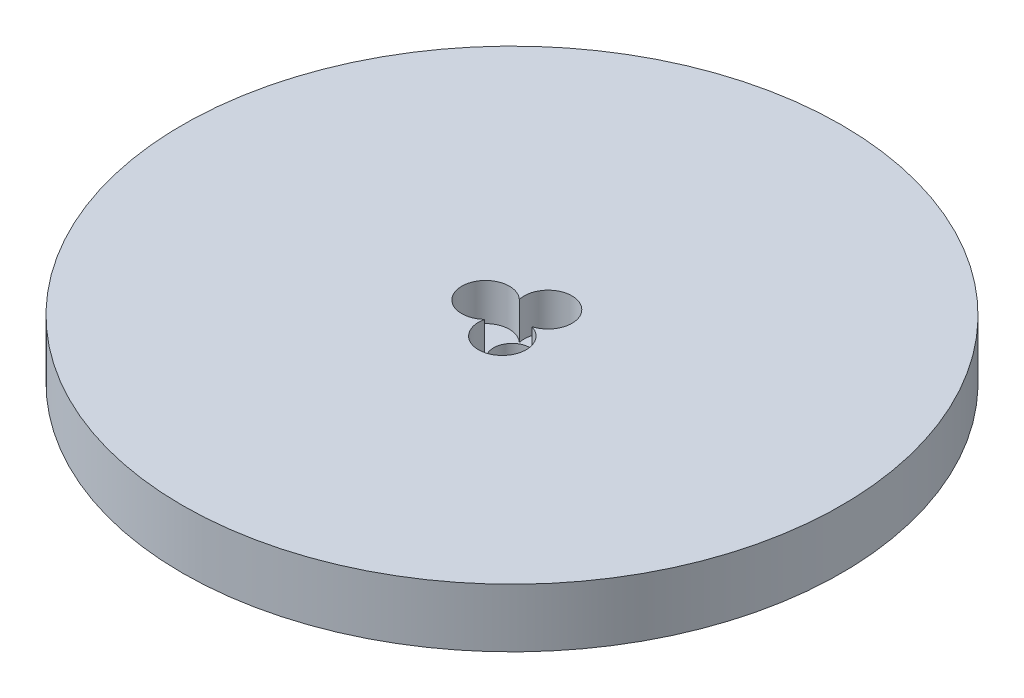
SolidWorks part; units mm, degrees
ref_plane "Front Plane" through (0, 0, 0) normal (0, 0, 1) x (1, 0, 0)
ref_plane "Top Plane" through (0, 0, 0) normal (0, 1, 0) x (1, 0, 0)
ref_plane "Right Plane" through (0, 0, 0) normal (1, 0, 0) x (0, 0, -1)
sketch "Sketch1" plane through (0, 0, 0) normal (0, 1, 0) x (1, 0, 0)
  circle A0 centre (0, 0) radius 90
  dimension "FLANGE_OD" = 180
extrude "Boss-Extrude1" add sketch "Sketch1" along normal blind 16
sketch "Sketch2" plane through (0, 0, 0) normal (0, 1, 0) x (1, 0, 0)
  circle A0 centre (0, 0) radius 5
  dimension "BORE_D" = 10
extrude "Cut-Extrude1" cut sketch "Sketch2" along normal through all
sketch "Sketch3" plane through (0, 16, 0) normal (0, 1, 0) x (1, 0, 0)
  circle A0 centre (0, 0) radius 7.2145 construction
  circle A1 centre (-7.2145, 0) radius 6.5138
  dimension "BOLT_D" = 13.0276
  dimension "BOLT_PCD" = 14.4291
extrude "Cut-Extrude2" cut sketch "Sketch3" against normal blind 10.2015
pattern_circular "CirPattern1" count 3 over 360 about axis through (0, 0, 0) along (0, 1, 0) of "Cut-Extrude2"
